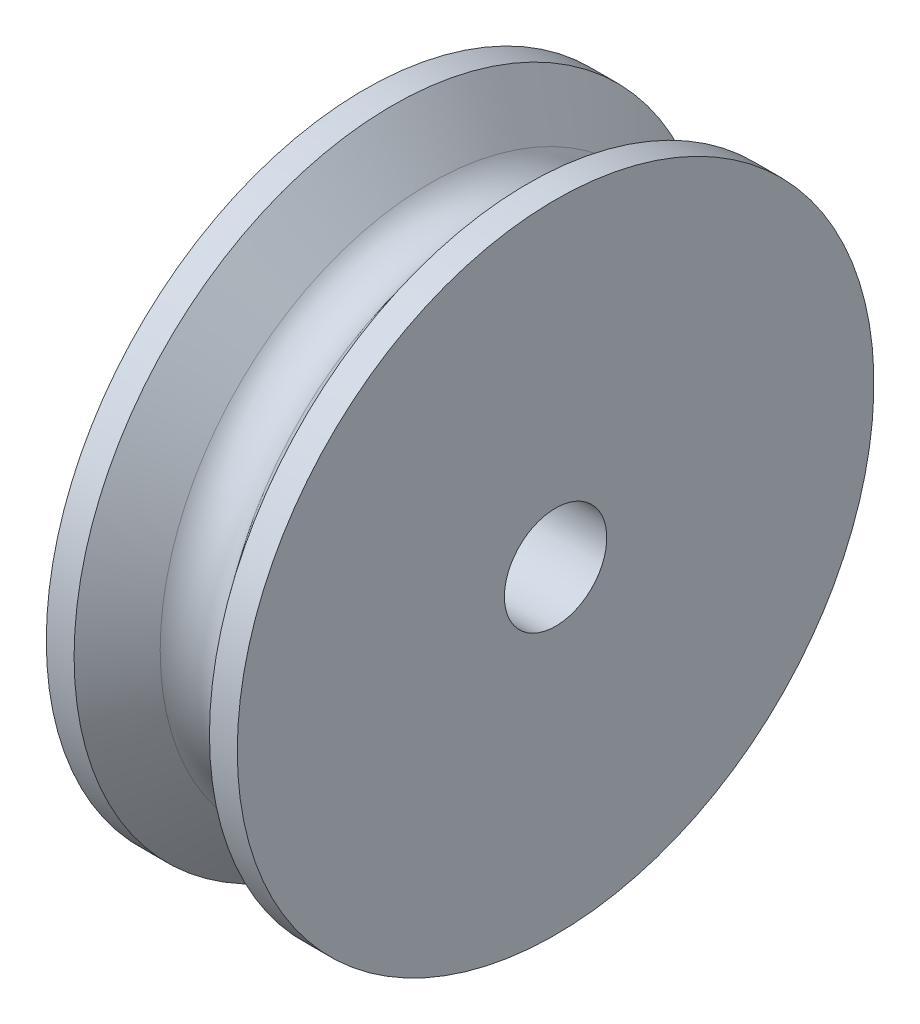
SolidWorks part; units mm, degrees
material "PET"
ref_plane "Front" through (0, 0, 0) normal (0, 0, 1) x (1, 0, 0)
ref_plane "Top" through (0, 0, 0) normal (0, 1, 0) x (1, 0, 0)
ref_plane "Right" through (0, 0, 0) normal (1, 0, 0) x (0, 0, -1)
sketch "Sketch1" plane through (0, 0, 0) normal (0, 0, 1) x (1, 0, 0)
  line L0 (0, 0) -> (5.8583, 0) construction
  line L1 (0, 2.5527) -> (9.525, 2.5527)
  line L2 (9.525, 2.5527) -> (9.525, 15.875)
  line L3 (9.525, 15.875) -> (8.1382, 15.875)
  line L4 (8.1382, 15.875) -> (6.2738, 13.4453)
  line L5 (3.2512, 13.4453) -> (1.3868, 15.875)
  line L6 (1.3868, 15.875) -> (0, 15.875)
  line L7 (0, 15.875) -> (0, 2.5527)
  arc A0 (6.2738, 13.4453) -> (3.2512, 13.4453) centre (4.7625, 14.605) cw
  dimension "D1" = 25.4
  dimension "D2" = 3.81
  dimension "D3" = 3.175
  dimension "D4" = 5.1054
  dimension "D5" = 75
  dimension "D6" = 9.525
revolve "Revolve1" add sketch "Sketch1" angle 360 about L0
